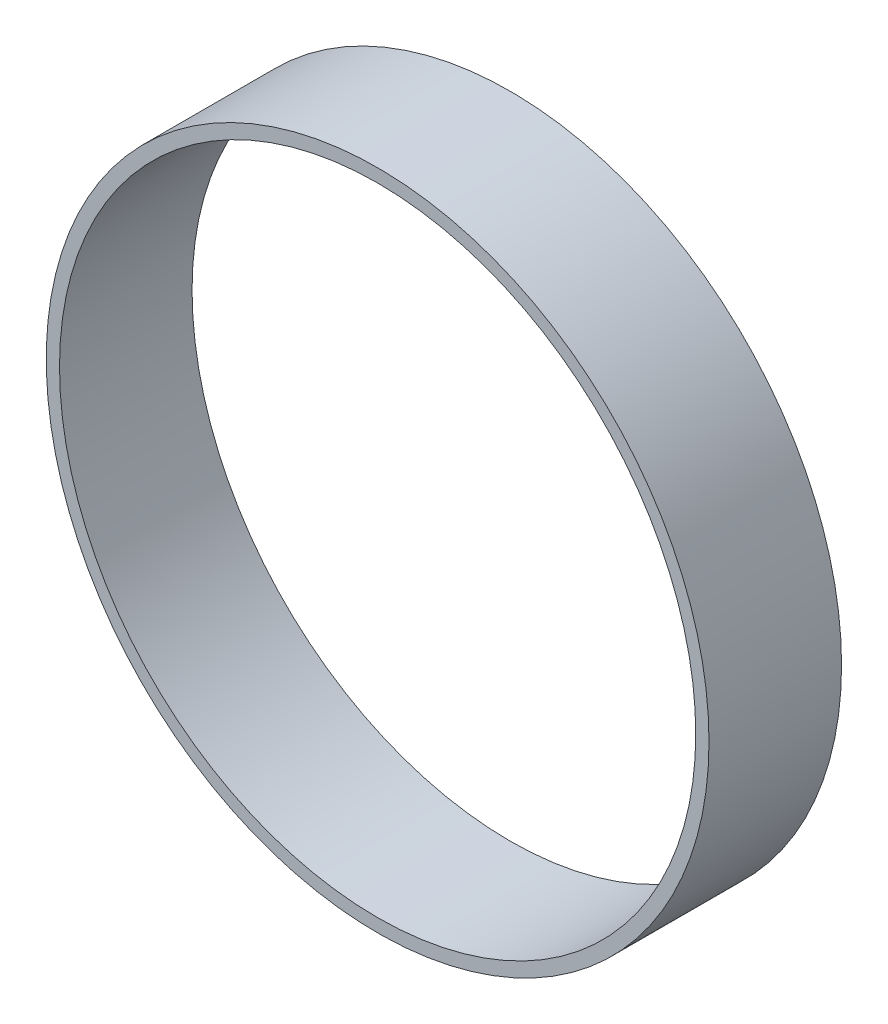
SolidWorks part; units mm, degrees
ref_plane "Front Plane" through (0, 0, 0) normal (0, 0, 1) x (1, 0, 0)
ref_plane "Top Plane" through (0, 0, 0) normal (0, 1, 0) x (1, 0, 0)
ref_plane "Right Plane" through (0, 0, 0) normal (1, 0, 0) x (0, 0, -1)
sketch "Sketch1" plane through (0, 0, 0) normal (0, 0, 1) x (1, 0, 0)
  circle A0 centre (0, 0) radius 75
  circle A1 centre (0, 0) radius 72
  dimension "D1" = 150
  dimension "D2" = 3
extrude "Boss-Extrude1" add sketch "Sketch1" along normal blind 30
